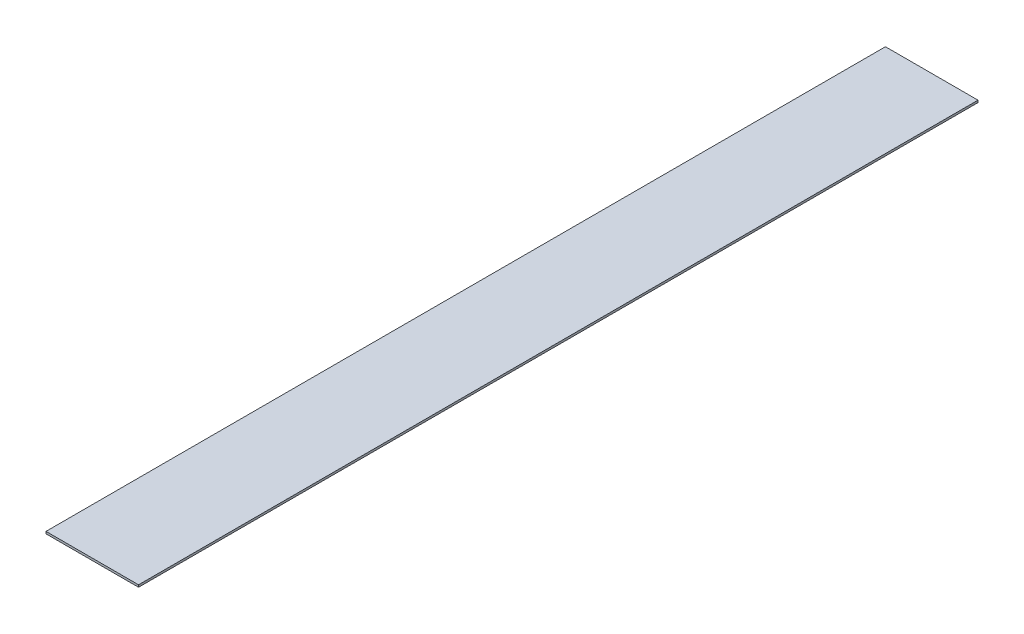
SolidWorks part; units mm, degrees
ref_plane "Front Plane" through (0, 0, 0) normal (0, 0, 1) x (1, 0, 0)
ref_plane "Top Plane" through (0, 0, 0) normal (0, 1, 0) x (1, 0, 0)
ref_plane "Right Plane" through (0, 0, 0) normal (1, 0, 0) x (0, 0, -1)
sketch "Sketch2" plane through (0, 0, 0) normal (0, 1, 0) x (1, 0, 0)
  line L0 (2.15, -19.5) -> (2.15, 19.5)
  line L1 (-2.15, -19.5) -> (-2.15, 19.5)
  line L2 (2.15, -19.5) -> (-2.15, -19.5)
  line L3 (2.15, 19.5) -> (-2.15, 19.5)
  line L4 (2.15, 19.5) -> (-2.15, -19.5) construction
  line L5 (-2.15, 19.5) -> (2.15, -19.5) construction
  point P2 (0, -19.5)
  point P5 (0, 19.5)
  point P6 (0, 0)
  dimension "D1" = 39
  dimension "D2" = 4.3
extrude "Boss-Extrude1" add sketch "Sketch2" along normal mid plane 0.1
